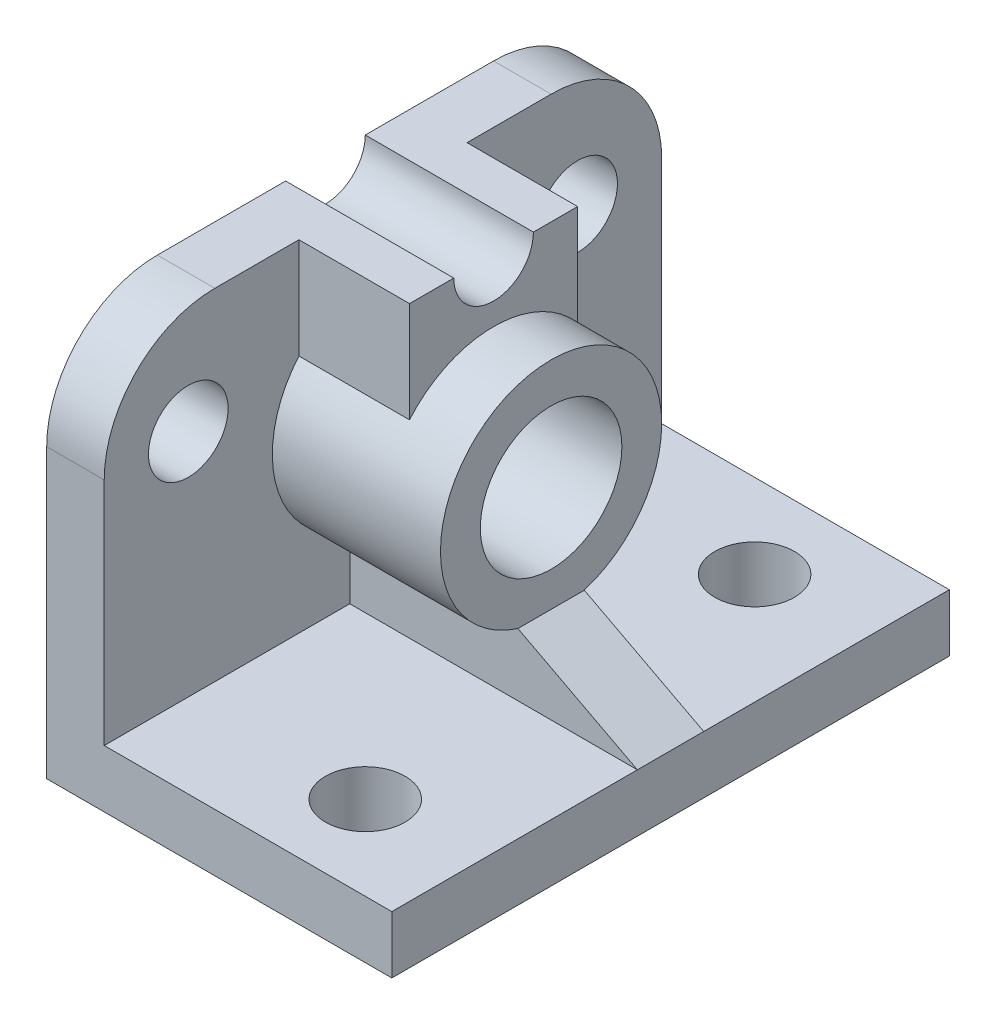
SolidWorks part; units mm, degrees
other "Markup1"
sketch "Sketch8" plane through (78, 90, 63) normal (0.7089, 0.4079, 0.5754) x (0.6543, -0.0758, -0.7524)
material "Alloy Steel"
ref_plane "Front Plane" through (0, 0, 0) normal (0, 0, 1) x (1, 0, 0)
ref_plane "Top Plane" through (0, 0, 0) normal (0, 1, 0) x (1, 0, 0)
ref_plane "Right Plane" through (0, 0, 0) normal (1, 0, 0) x (0, 0, -1)
sketch "Sketch1" plane through (0, 0, 0) normal (0, 0, 1) x (1, 0, 0)
  line L2 (0, 0) -> (0, 90)
  line L3 (0, 90) -> (13, 90)
  line L4 (13, 13) -> (13, 90)
  line L5 (0, 0) -> (78, 0)
  line L7 (13, 13) -> (78, 13)
  line L8 (78, 0) -> (78, 13)
  dimension "D1" = 90
  dimension "D2" = 78
  dimension "D3" = 13
  dimension "D4" = 13
extrude "Boss-Extrude1" add sketch "Sketch1" along normal mid plane 126
sketch "Sketch2" plane through (13, 0, 0) normal (1, 0, 0) x (0, 0, -1)
  line L0 (-63, 90) -> (63, 90) construction
  line L1 (-19, 90) -> (19, 90)
  line L2 (19, 90) -> (19, 67.2481)
  line L3 (-19, 90) -> (-19, 67.2481)
  line L4 (-63, 13) -> (63, 13) construction
  line L5 (7.5, 13) -> (7.5, 27.1515)
  line L6 (-63, 13) -> (63, 13) construction
  line L8 (-7.5, 27.1515) -> (-7.5, 13)
  line L9 (-7.5, 13) -> (7.5, 13)
  line L10 (-7.5, 27.1515) -> (7.5, 27.1515)
  circle A0 centre (0, 51) radius 25
  circle A1 centre (0, 51) radius 16
  arc A2 (-9, 90) -> (9, 90) centre (0, 90) ccw
  point P17 (0, 13)
  line M7 (63, 90) -> (-63, 90)
  line M9 (-63, 13) -> (63, 13)
  dimension "D1" = 50
  dimension "D2" = 32
  dimension "D4" = 9
  dimension "D3" = 38
  dimension "D5" = 10
  dimension "D6" = 15
extrude "Boss-Extrude2" add sketch "Sketch2" along normal blind 38 contours A0 A1 region at (13, 75.301, 0)
extrude "Boss-Extrude3" add sketch "Sketch2<3>" along normal blind 25 contours A2 L3 A0 L2 M7 region at (13, 80.2887, 0)
sketch "Sketch2<3>" plane through (13, 0, 0) normal (1, 0, 0) x (0, 0, -1) same geometry as "Sketch2"
extrude "Cut-Extrude1" cut sketch "Sketch2<4>" against normal blind 38 contours L1 A2 region at (13, 86.1803, 0)
sketch "Sketch2<4>" plane through (13, 0, 0) normal (1, 0, 0) x (0, 0, -1) same geometry as "Sketch2"
extrude "Cut-Extrude2" cut sketch "Sketch2<5>" against normal blind 38 contours A1 region at (13, 51, 0)
sketch "Sketch2<5>" plane through (13, 0, 0) normal (1, 0, 0) x (0, 0, -1) same geometry as "Sketch2"
extrude "Boss-Extrude4" add sketch "Sketch2<6>" along normal up to vertex (65 mm away) contours A0 L8 L5 M9 | L10 A0 region at (13, 19.6945, 0) region at (13, 26.69, 0) up to point (78, 13, 63)
sketch "Sketch2<6>" plane through (13, 0, 0) normal (1, 0, 0) x (0, 0, -1) same geometry as "Sketch2"
sketch "Sketch5" plane through (13, 0, 0) normal (1, 0, 0) x (0, 0, -1)
  line L0 (-63, 13) -> (-63, 90) construction
  line L1 (-63, 90) -> (-19, 90) construction
  circle A0 centre (-44, 65) radius 9
  dimension "D3" = 18
  dimension "D1" = 19
  dimension "D2" = 25
extrude "Cut-Extrude4" cut sketch "Sketch5" against normal blind 38
mirror "Mirror1" about plane through (0, 0, 0) normal (0, 0, 1) of "Cut-Extrude4"
sketch "Sketch6" plane through (0, 13, 0) normal (0, 1, 0) x (1, 0, 0)
  line L0 (78, -63) -> (78, -7.5) construction
  line L1 (78, -63) -> (13, -63) construction
  circle A0 centre (53, -44) radius 9
  dimension "D3" = 18
  dimension "D1" = 25
  dimension "D2" = 19
extrude "Cut-Extrude5" cut sketch "Sketch6" against normal blind 38
mirror "Mirror2" about plane through (0, 0, 0) normal (0, 0, 1) of "Cut-Extrude5"
fillet "Fillet1" radius 25 2 edges at (6.5, 90, -63) (6.5, 90, 63)
sketch "Sketch7" plane through (0, 0, 7.5) normal (0, 0, 1) x (1, 0, 0)
  line L0 (51, 27.1515) -> (78, 13)
  line L1 (78, 13) -> (78, 27.1515)
  line L2 (78, 27.1515) -> (51, 27.1515)
extrude "Cut-Extrude6" cut sketch "Sketch7" against normal blind 38
